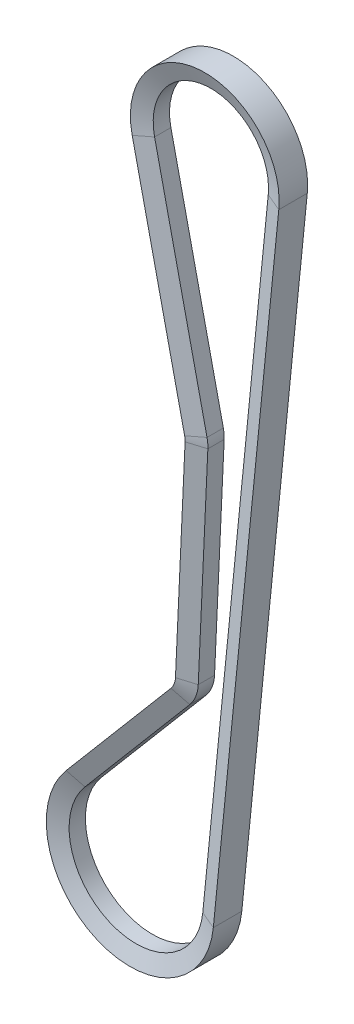
SolidWorks part; units mm, degrees
ref_plane "Front Plane" through (0, 0, 0) normal (0, 0, 1) x (1, 0, 0)
ref_plane "Top Plane" through (0, 0, 0) normal (0, 1, 0) x (1, 0, 0)
ref_plane "Right Plane" through (0, 0, 0) normal (1, 0, 0) x (0, 0, -1)
sketch "Sketch2" plane through (0, 0, 0) normal (0, 0, 1) x (1, 0, 0)
  line L0 (0, 0) -> (1, 0) construction
  line L1 (0, 0) -> (0, 1) construction
  line L12 (24.7515, -2.4759) -> (2.8567, -221.3613)
  line L14 (-46.3636, -200.4697) -> (-11.3088, -159.1135)
  line L15 (-9.8095, -155.2999) -> (-6.5871, -85.3741)
  line L16 (-6.7341, -83.693) -> (-24.2728, -5.4402)
  arc A4 (2.8567, -221.3613) -> (-46.3636, -200.4697) centre (-25.0043, -218.5744) cw
  arc A7 (-24.2728, -5.4402) -> (24.7515, -2.4759) centre (0, 0) cw
  arc A8 (-11.3088, -159.1135) -> (-9.8095, -155.2999) centre (-16.1528, -155.0076) ccw
  arc A9 (-6.5871, -85.3741) -> (-6.7341, -83.693) centre (-12.9304, -85.0818) ccw
ref_plane "Plane4" through (-24.2728, -5.4402, 0) normal (-0.2187, 0.9758, 0) x (0.9758, 0.2187, 0)
sketch "Sketch3" plane through (-24.2728, -5.4402, 0) normal (-0.2187, 0.9758, 0) x (0.9758, 0.2187, 0)
  line L0 (0, -4.7625) -> (0, 4.7625)
  line L1 (0, -4.7625) -> (5.588, -2.7286)
  line L2 (5.588, -2.7286) -> (5.588, 2.7286)
  line L3 (5.588, 2.7286) -> (0, 4.7625)
  line L4 (0, 0) -> (5.588, 0) construction
  dimension "D1" = 9.525
  dimension "D2" = 5.588
  dimension "D3" = 40
sweep "Sweep1" add profiles "Sketch3" path "Sketch2"
